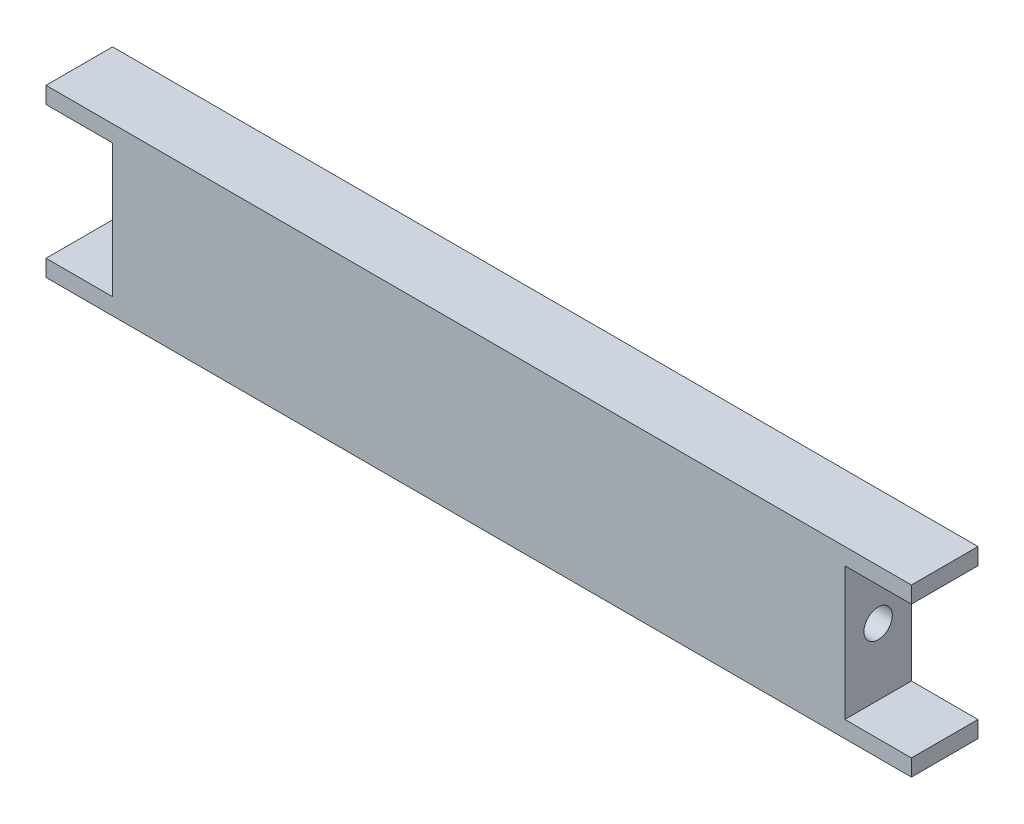
SolidWorks part; units mm, degrees
material "6061-T6 (SS)"
ref_plane "Front" through (0, 0, 0) normal (0, 0, 1) x (1, 0, 0)
ref_plane "Top" through (0, 0, 0) normal (0, 1, 0) x (1, 0, 0)
ref_plane "Right" through (0, 0, 0) normal (1, 0, 0) x (0, 0, -1)
sketch "Sketch1" plane through (0, 0, 0) normal (0, 0, 1) x (1, 0, 0)
  line L0 (0, 7.9375) -> (0, -7.9375) construction
  line L1 (-41.275, -7.9375) -> (41.275, -7.9375)
  line L2 (-41.275, -7.9375) -> (-41.275, -6.35)
  line L3 (-41.275, 7.9375) -> (41.275, 7.9375)
  line L4 (41.275, -7.9375) -> (41.275, -6.35)
  line L5 (-41.275, -7.9375) -> (41.275, 7.9375) construction
  line L6 (-41.275, 7.9375) -> (41.275, -7.9375) construction
  line L7 (-41.275, 6.35) -> (-34.925, 6.35)
  line L8 (41.275, 6.35) -> (41.275, 7.9375)
  line L9 (-41.275, -6.35) -> (-34.925, -6.35)
  line L10 (-34.925, 6.35) -> (-34.925, -6.35)
  line L11 (41.275, -6.35) -> (34.925, -6.35)
  line L12 (41.275, 6.35) -> (34.925, 6.35)
  line L13 (34.925, 6.35) -> (34.925, -6.35)
  line L14 (-41.275, 6.35) -> (-41.275, 7.9375)
  point P0 (0, 0)
  dimension "D1" = 82.55
  dimension "D2" = 15.875
  dimension "D3" = 1.5875
  dimension "D4" = 1.5875
  dimension "D5" = 6.35
extrude "Boss-Extrude1" add sketch "Sketch1" along normal blind 6.35
hole_wizard "Tap Drill for #6-32 Tap1" positions "Sketch3" profile "Sketch4" hole size "#6-32" standard "ANSI Inch"
sketch "Sketch3" plane through (34.925, 0, 0) normal (1, 0, 0) x (0, 0, -1)
  line L0 (-6.35, 7.9375) -> (0, 7.9375) construction
  line L1 (-6.35, -7.9375) -> (0, -7.9375) construction
  line L2 (-6.35, -6.35) -> (0, -6.35) construction
  point P0 (-3.175, 0)
  point P2 (-3.175, 0)
  point P12 (-3.175, -6.35)
  dimension "D1" = 7.9375
  dimension "D2" = 7.9375
sketch "Sketch4" plane through (34.925, 0, 3.175) normal (0, 1, 0) x (0, 0, -1)
  line L0 (0, 0) -> (0, 7.1627)
  line L1 (0, 7.1627) -> (1.3525, 6.35)
  line L2 (1.3525, 6.35) -> (1.3525, 0)
  line L5 (1.3525, 0) -> (0, 0)
  line L10 (0, 7.1627) -> (-1.3525, 6.35) construction
  line L11 (0, -6.35) -> (0, 107.95) construction
  dimension "Hole Dia." = 2.7051
  dimension "Hole Depth" = 6.35
  dimension "Drill Angle" = 118
ref_plane "Plane1" through (0, 0, 0) normal (-1, 0, 0) x (0, 0, 1)
mirror "Mirror1" about plane through (0, 0, 0) normal (-1, 0, 0) of "Tap Drill for #6-32 Tap1"
